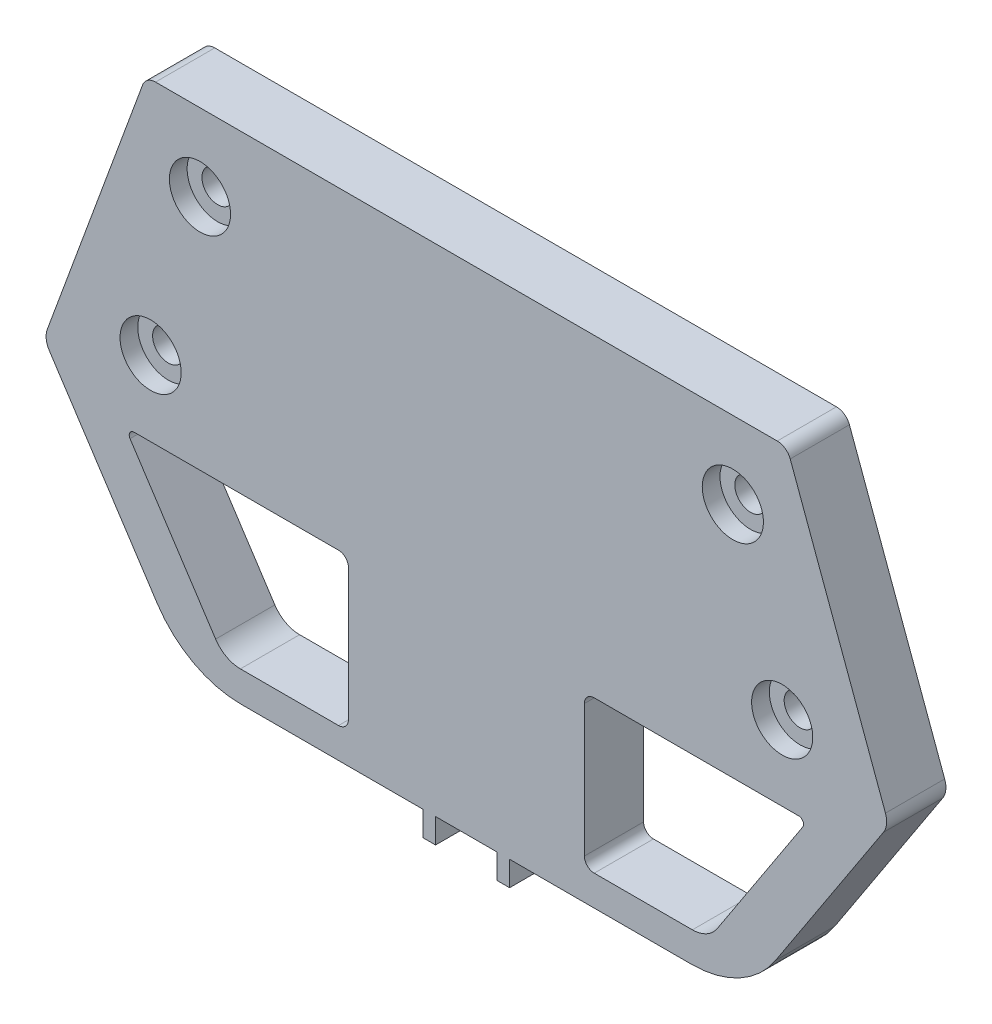
SolidWorks part; units mm, degrees
ref_plane "Front Plane" through (0, 0, 0) normal (0, 0, 1) x (1, 0, 0)
ref_plane "Top Plane" through (0, 0, 0) normal (0, 1, 0) x (1, 0, 0)
ref_plane "Right Plane" through (0, 0, 0) normal (1, 0, 0) x (0, 0, -1)
sketch "Sketch2" plane through (0, 0, 0) normal (0, 0, 1) x (1, 0, 0)
  line L0 (0, -44.7145) -> (0, 43.9236) construction
  line L3 (-53.9331, -0.3154) -> (-41.6738, 33.03)
  line L5 (-53.6746, -2.5826) -> (-39.7807, -23.8164)
  line L8 (-28.9986, -29.6465) -> (28.9986, -29.6465)
  line L9 (-40.005, 34.1945) -> (40.005, 34.1945)
  line L10 (53.6746, -2.5826) -> (39.7807, -23.8164)
  line L11 (53.9331, -0.3154) -> (41.6738, 33.03)
  arc A1 (-40.005, 34.1945) -> (-41.6738, 33.03) centre (-40.005, 32.4165) ccw
  arc A6 (-28.9986, -29.6465) -> (-39.7807, -23.8164) centre (-28.9986, -16.7614) cw
  arc A8 (-53.6746, -2.5826) -> (-53.9331, -0.3154) centre (-51.5491, -1.1919) cw
  arc A10 (53.6746, -2.5826) -> (53.9331, -0.3154) centre (51.5491, -1.1919) ccw
  arc A11 (28.9986, -29.6465) -> (39.7807, -23.8164) centre (28.9986, -16.7614) ccw
  arc A13 (40.005, 34.1945) -> (41.6738, 33.03) centre (40.005, 32.4165) cw
  point P4 (0, 57.6776)
  point P9 (0, 19.5776)
  point P12 (54.3738, -1.514)
  point P13 (0, -29.6465)
  point P19 (-35.9659, -29.6465)
  point P20 (0, -3.9055)
  point P28 (-54.3738, -1.514)
  point P33 (0, 34.1945)
  point P34 (35.9659, -29.6465)
  dimension "D2" = 1.778
  dimension "D3" = 12.8851
  dimension "D6" = 28.9986
  dimension "D4" = 2.54
  dimension "D7" = 35.9659
  dimension "D8" = 40.005
  dimension "D9" = 41.6738
  dimension "D10" = 51.5491
  dimension "D12" = 19.5776
  dimension "D13" = 32.4165
  dimension "D14" = 57.6776
extrude "Boss-Extrude1" add sketch "Sketch2" along normal blind 7.62
sketch "Sketch6" plane through (0, 0, 7.62) normal (0, 0, 1) x (1, 0, 0)
  line L0 (0, -25.1696) -> (0, 28.2164) construction
  line L3 (-43.2885, -7.1893) -> (-32.2734, -24.0235)
  line L4 (-53.6746, -2.5826) -> (-39.7807, -23.8164) construction
  line L5 (-54.0728, -1.4797) -> (0, -1.4797) construction
  line L6 (-42.7572, -6.2066) -> (-16.453, -6.2066)
  line L7 (-15.183, -7.4766) -> (-15.183, -24.4774)
  line L13 (-29.0853, -25.7474) -> (-16.453, -25.7474)
  line L14 (43.2885, -7.1893) -> (32.2734, -24.0235)
  line L17 (29.0853, -25.7474) -> (16.453, -25.7474)
  line L18 (15.183, -7.4766) -> (15.183, -24.4774)
  line L19 (42.7572, -6.2066) -> (16.453, -6.2066)
  line L20 (-11.43, -10.9992) -> (-11.43, -29.6465) construction
  line L21 (-28.9986, -29.6465) -> (28.9986, -29.6465) construction
  arc A3 (-53.9331, -0.3154) -> (-53.6746, -2.5826) centre (-51.5491, -1.1919) ccw construction
  arc A6 (-15.183, -7.4766) -> (-16.453, -6.2066) centre (-16.453, -7.4766) ccw
  arc A7 (-42.7572, -6.2066) -> (-43.2885, -7.1893) centre (-42.7572, -6.8416) ccw
  arc A12 (-29.0853, -25.7474) -> (-32.2734, -24.0235) centre (-29.0853, -21.9374) cw
  arc A13 (-15.183, -24.4774) -> (-16.453, -25.7474) centre (-16.453, -24.4774) cw
  arc A14 (42.7572, -6.2066) -> (43.2885, -7.1893) centre (42.7572, -6.8416) cw
  arc A15 (29.0853, -25.7474) -> (32.2734, -24.0235) centre (29.0853, -21.9374) ccw
  arc A16 (15.183, -24.4774) -> (16.453, -25.7474) centre (16.453, -24.4774) ccw
  arc A17 (15.183, -7.4766) -> (16.453, -6.2066) centre (16.453, -7.4766) cw
  dimension "D1" = 3.81
  dimension "D2" = 1.27
  dimension "D3" = 26.613
  dimension "D4" = 0.635
  dimension "D5" = 40.5153
  dimension "D6" = 54.1872
  dimension "D7" = 3.8991
extrude "Cut-Extrude4" cut sketch "Sketch6" against normal through all
sketch "Sketch8" plane through (0, 0, 7.62) normal (0, 0, 1) x (1, 0, 0)
  line L0 (0, 24.5882) -> (0, -31.804) construction
  line L1 (-16.453, -6.2066) -> (-42.7572, -6.2066) construction
  circle A0 centre (-40.64, 3.4454) radius 2.032
  circle A1 centre (-34.29, 24.2734) radius 2.032
  circle A2 centre (40.64, 3.4454) radius 2.032
  circle A3 centre (34.29, 24.2734) radius 2.032
  dimension "D1" = 4.064
  dimension "D2" = 4.064
  dimension "D3" = 40.64
  dimension "D4" = 34.29
  dimension "D5" = 9.652
  dimension "D6" = 30.48
extrude "Cut-Extrude6" cut sketch "Sketch8" against normal through all
sketch "Sketch9" plane through (0, -29.6465, 0) normal (0, -1, 0) x (1, 0, 0)
  line L0 (0, -14.4205) -> (0, 21.768) construction
  line L1 (-28.9986, 3.81) -> (28.9986, 3.81) construction
  line L2 (-28.9986, 7.62) -> (-28.9986, 0) construction
  line L3 (28.9986, 7.62) -> (28.9986, 0) construction
  circle A0 centre (0, 3.81) radius 2.032
  dimension "D1" = 4.064
extrude "Cut-Extrude7" cut sketch "Sketch9" against normal blind 25.4
sketch "Sketch11" plane through (0, 0, 7.62) normal (0, 0, 1) x (1, 0, 0)
  line L0 (0, 31.297) -> (0, -23.5528) construction
  circle A0 centre (-34.29, 24.2734) radius 3.937
  circle A1 centre (-40.64, 3.4454) radius 3.937
  circle A2 centre (40.64, 3.4454) radius 3.937
  circle A3 centre (34.29, 24.2734) radius 3.937
  dimension "D1" = 7.874
  dimension "D2" = 7.874
extrude "Cut-Extrude9" cut sketch "Sketch11" against normal blind 2.286
sketch "Sketch12" plane through (0, 0, 7.62) normal (0, 0, 1) x (1, 0, 0)
  line L0 (-28.9986, -29.6465) -> (28.9986, -29.6465) construction
  line L1 (-5.5563, -32.8215) -> (-3.9688, -32.8215)
  line L2 (-5.5563, -32.8215) -> (-5.5563, -29.6465)
  line L3 (-5.5563, -29.6465) -> (-3.9688, -29.6465)
  line L4 (-3.9688, -32.8215) -> (-3.9688, -29.6465)
  line L5 (-5.5563, -32.8215) -> (-3.9688, -29.6465) construction
  line L6 (-5.5563, -29.6465) -> (-3.9688, -32.8215) construction
  line L7 (-3.9688, -29.6465) -> (0, -29.6465) construction
  line L8 (5.5563, -32.8215) -> (3.9688, -32.8215)
  line L9 (5.5563, -32.8215) -> (5.5563, -29.6465)
  line L10 (5.5563, -29.6465) -> (3.9688, -29.6465)
  line L11 (3.9688, -32.8215) -> (3.9688, -29.6465)
  line L12 (5.5563, -32.8215) -> (3.9688, -29.6465) construction
  line L13 (5.5563, -29.6465) -> (3.9688, -32.8215) construction
  line L14 (0, -29.6465) -> (3.9688, -29.6465) construction
  point P0 (-4.7625, -31.234)
  point P7 (4.7625, -31.234)
  point P12 (0, 0)
  dimension "D1" = 7.9375
  dimension "D2" = 1.5875
  dimension "D3" = 3.175
extrude "Boss-Extrude2" add sketch "Sketch12" against normal up to surface (7.62 mm away) up to face at (-38.608, 3.4454, 0)
